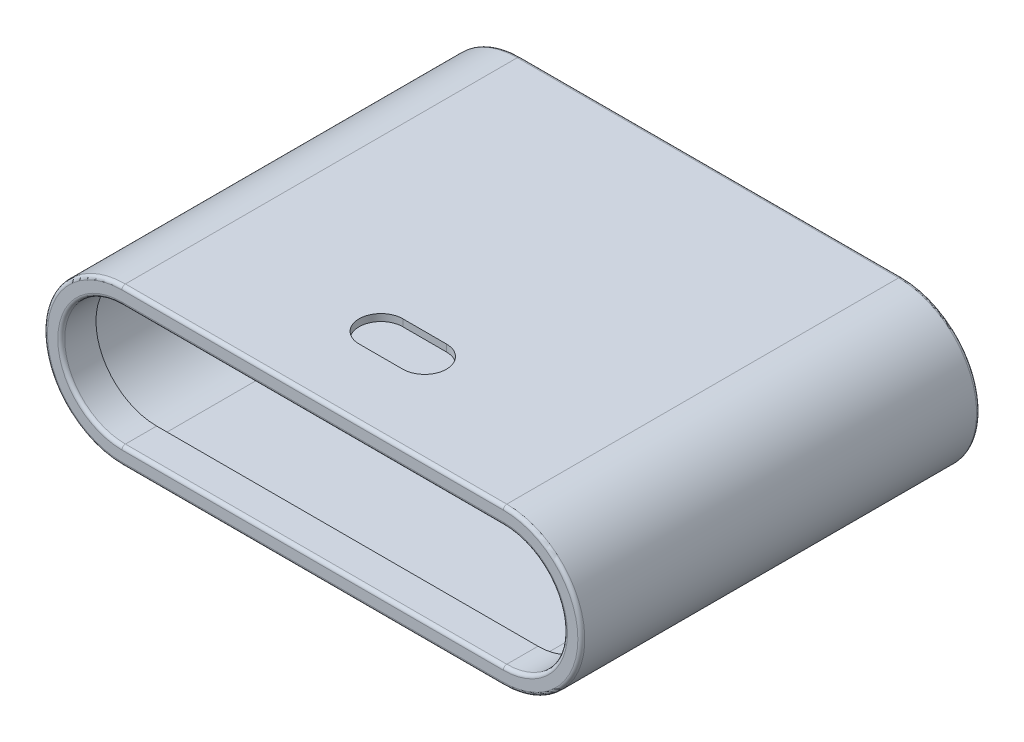
SolidWorks part; units mm, degrees
ref_plane "Plan de face" through (0, 0, 0) normal (0, 0, 1) x (1, 0, 0)
ref_plane "Plan de dessus" through (0, 0, 0) normal (0, 1, 0) x (1, 0, 0)
ref_plane "Plan de droite" through (0, 0, 0) normal (1, 0, 0) x (0, 0, -1)
sketch "Esquisse1" plane through (0, 0, 0) normal (0, 0, 1) x (1, 0, 0)
  line L0 (-55, 0) -> (55, 0) construction
  line L1 (-55, 22.5) -> (55, 22.5)
  line L2 (-55, -22.5) -> (55, -22.5)
  arc A0 (-55, 22.5) -> (-55, -22.5) centre (-55, 0) ccw
  arc A1 (55, -22.5) -> (55, 22.5) centre (55, 0) ccw
  point P2 (0, 0)
  dimension "D1" = 110
  dimension "D2" = 45
extrude "Boss.-Extru.1" add sketch "Esquisse1" along normal blind 115 contours L1 A1 L2 A0
sketch "Esquisse2" plane through (0, 0, 115) normal (0, 0, 1) x (1, 0, 0)
  line L4 (-55, -17.5) -> (55, -17.5)
  line L5 (55, 17.5) -> (-55, 17.5)
  line L6 (-55, -17.5) -> (55, -17.5)
  line L7 (55, 17.5) -> (-55, 17.5)
  arc A4 (-55, 17.5) -> (-55, -17.5) centre (-55, 0) ccw
  arc A5 (55, -17.5) -> (55, 17.5) centre (55, 0) ccw
  arc A6 (-55, 17.5) -> (-55, -17.5) centre (-55, 0) ccw
  arc A7 (55, -17.5) -> (55, 17.5) centre (55, 0) ccw
  dimension "D1" = 5
extrude "Enlèv. mat.-Extru.1" cut sketch "Esquisse2" against normal blind 10
sketch "Esquisse3" plane through (0, 0, 0) normal (0, 0, -1) x (-1, 0, 0)
  line L4 (55, 20.5) -> (-55, 20.5)
  line L5 (-55, -20.5) -> (55, -20.5)
  line L6 (55, 20.5) -> (-55, 20.5)
  line L7 (-55, -20.5) -> (55, -20.5)
  arc A4 (55, -20.5) -> (55, 20.5) centre (55, 0) ccw
  arc A5 (-55, 20.5) -> (-55, -20.5) centre (-55, 0) ccw
  arc A6 (55, -20.5) -> (55, 20.5) centre (55, 0) ccw
  arc A7 (-55, 20.5) -> (-55, -20.5) centre (-55, 0) ccw
  dimension "D1" = 2
extrude "Enlèv. mat.-Extru.2" cut sketch "Esquisse3" against normal up to surface (105 mm away) up to face at (0, 0, 105)
ref_plane "Plan1" through (0, 0, 5) normal (0, 0, -1) x (-1, 0, 0)
sketch "Esquisse4" plane through (0, 0, 5) normal (0, 0, -1) x (-1, 0, 0)
  line L0 (-75.5, 0) -> (-71.5, 0) construction
  arc A0 (-74.128, 7.3734) -> (-74.128, -7.3734) centre (-75.5, 0) cw
  arc A1 (-55, 20.5) -> (-55, -20.5) centre (-55, 0) ccw construction
  arc A2 (-55, 20.5) -> (-55, -20.5) centre (-55, 0) ccw construction
  arc A3 (-74.128, 7.3734) -> (-74.128, -7.3734) centre (-55, 0) ccw
  circle A4 centre (-71.5, 0) radius 2
  dimension "D1" = 7.5
  dimension "D3" = 4
  dimension "D2" = 4
extrude "Boss.-Extru.2" add sketch "Esquisse4" against normal blind 5
mirror "Symétrie1" about plane through (0, 0, 0) normal (1, 0, 0) of "Boss.-Extru.2"
chamfer "Chanfrein1" distance 7.5 angle 45 2 edges at (75.5, 0, 10) (-75.5, 0, 10)
sketch "Esquisse5" plane through (0, 22.5, 0) normal (0, 1, 0) x (1, 0, 0)
  line L0 (-6.3, -89) -> (6.3, -89) construction
  line L1 (-6.3, -82.7) -> (6.3, -82.7)
  line L2 (-6.3, -95.3) -> (6.3, -95.3)
  line L3 (0, 0) -> (0, -89) construction
  line L4 (-55, -115) -> (55, -115) construction
  arc A0 (-6.3, -82.7) -> (-6.3, -95.3) centre (-6.3, -89) ccw
  arc A1 (6.3, -95.3) -> (6.3, -82.7) centre (6.3, -89) ccw
  point P2 (0, -89)
  dimension "D1" = 12.6
  dimension "D2" = 12.6
  dimension "D3" = 26
extrude "Enlèv. mat.-Extru.3" cut sketch "Esquisse5" against normal up to next
fillet "Congé1" radius 1 12 edges at (0, 22.5, 0) (77.5, 0, 0) (0, -22.5, 0) (0, 17.5, 115) (72.5, 0, 115) (0, -17.5, 115) (0, 22.5, 115) (77.5, 0, 115) (0, -22.5, 115) (-77.5, 0, 0) (-72.5, 0, 115) (-77.5, 0, 115)
